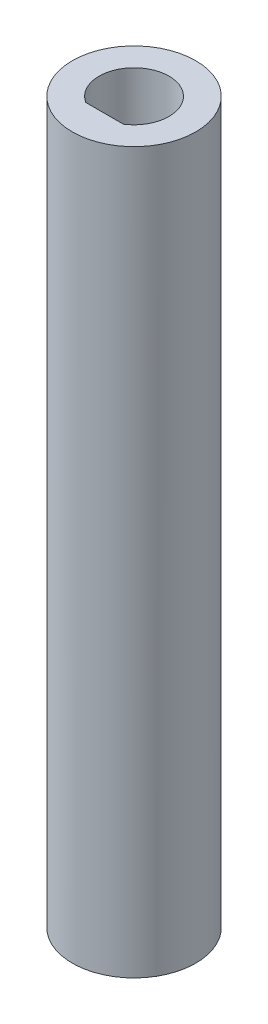
SolidWorks part; units mm, degrees
ref_plane "Front Plane" through (0, 0, 0) normal (0, 0, 1) x (1, 0, 0)
ref_plane "Top Plane" through (0, 0, 0) normal (0, 1, 0) x (1, 0, 0)
ref_plane "Right Plane" through (0, 0, 0) normal (1, 0, 0) x (0, 0, -1)
sketch "Sketch1" plane through (0, 0, 0) normal (0, 1, 0) x (1, 0, 0)
  line L0 (0, 0) -> (0, -3.2385) construction
  line L1 (0, 0) -> (3.2385, 0) construction
  line L2 (0, -2.7305) -> (1.7413, -2.7305) construction
  line L3 (1.7413, -2.7305) -> (-1.7413, -2.7305)
  circle A0 centre (0, 0) radius 3.2385 construction
  arc A1 (1.7413, -2.7305) -> (-1.7413, -2.7305) centre (0, 0) ccw
  circle A2 centre (0, 0) radius 5.715
  dimension "D1" = 6.477
  dimension "D3" = 11.43
  dimension "D2" = 0.508
extrude "Boss-Extrude1" add sketch "Sketch1" along normal blind 12.7
sketch "Sketch3" plane through (0, 0, 0) normal (0, -1, 0) x (-1, 0, 0)
  circle A0 centre (0, 0) radius 5.715
extrude "Boss-Extrude2" add sketch "Sketch3" along normal blind 53.975
sketch "Sketch4" plane through (0, -53.975, 0) normal (0, -1, 0) x (1, 0, 0)
  line L0 (0, 2.54) -> (-1.7961, 4.3361)
  line L1 (-2.54, -2.54) -> (2.54, -2.54) construction
  line L2 (-2.54, -2.54) -> (-2.54, 2.54) construction
  line L3 (-2.54, 2.54) -> (2.54, 2.54) construction
  line L4 (2.54, -2.54) -> (2.54, 2.54) construction
  line L5 (-2.54, -2.54) -> (2.54, 2.54) construction
  line L6 (-2.54, 2.54) -> (2.54, -2.54) construction
  line L7 (-2.54, 0) -> (-4.3361, 1.7961)
  line L8 (-4.3361, 1.7961) -> (-1.7961, 4.3361)
  line L9 (2.54, 0) -> (4.3361, -1.7961)
  line L10 (0, -2.54) -> (1.7961, -4.3361)
  line L11 (1.7961, -4.3361) -> (4.3361, -1.7961)
  line L12 (-2.54, 0) -> (-4.3361, -1.7961)
  line L13 (0, -2.54) -> (-1.7961, -4.3361)
  line L14 (-4.3361, -1.7961) -> (-1.7961, -4.3361)
  line L15 (2.54, 0) -> (4.3361, 1.7961)
  line L16 (1.7961, 4.3361) -> (4.3361, 1.7961)
  line L17 (0, 2.54) -> (1.7961, 4.3361)
  point P0 (0, 0)
  dimension "D1" = 2.54
  dimension "D2" = 5.08
  dimension "D3" = 5.08
  dimension "D4" = 8.6721
  dimension "D5" = 3.5921
  dimension "D6" = 3.5921
  dimension "D7" = 3.5921
  dimension "D8" = 3.5921
  dimension "D9" = 8.6721
  dimension "D10" = 0
  dimension "D11" = 3.5921
  dimension "D12" = 5.08
  dimension "D13" = 2.54
  dimension "D14" = 2.54
  dimension "D15" = 2.54
  dimension "D16" = 2.54
  dimension "D17" = 2.54
  dimension "D18" = 2.54
  dimension "D19" = 2.54
  dimension "D20" = 2.54
extrude "Cut-Extrude1" cut sketch "Sketch4" against normal blind 53.975
